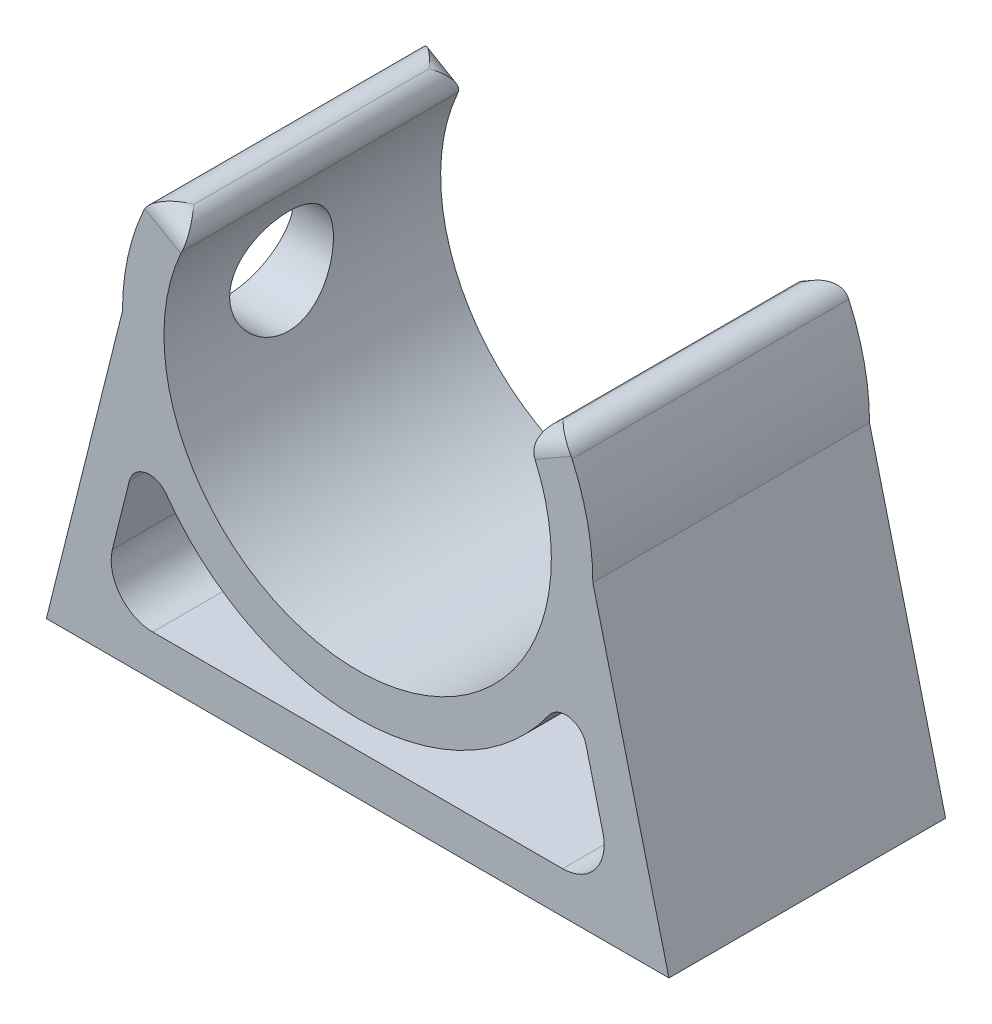
SolidWorks part; units mm, degrees
ref_plane "Front Plane" through (0, 0, 0) normal (0, 0, 1) x (1, 0, 0)
ref_plane "Top Plane" through (0, 0, 0) normal (0, 1, 0) x (1, 0, 0)
ref_plane "Right Plane" through (0, 0, 0) normal (1, 0, 0) x (0, 0, -1)
sketch "Sketch1" plane through (0, 0, 0) normal (0, 0, 1) x (1, 0, 0)
  line L0 (0.0802, 28.0625) -> (-0.0941, -32.9144) construction
  line L1 (0, 0) -> (14.7467, 8.4579) construction
  line L2 (12.1443, 6.9653) -> (14.7467, 8.4579)
  line L3 (-12.1043, 7.0346) -> (-14.6981, 8.5421)
  arc A0 (12.1443, 6.9653) -> (-12.1043, 7.0346) centre (0, 0) cw
  arc A1 (14.7467, 8.4579) -> (-14.6981, 8.5421) centre (0, 0) cw
  dimension "D1" = 14
  dimension "D2" = 3
  dimension "D3" = 120
extrude "Boss-Extrude1" add sketch "Sketch1" along normal blind 20
sketch "Sketch2" plane through (0, 0, 20) normal (0, 0, 1) x (1, 0, 0)
  line L0 (-17, 0) -> (-22.5, -22)
  line L1 (-22.5, -22) -> (22.5, -22)
  line L2 (22.5, -22) -> (17, 0)
  line L3 (17, 10.1614) -> (17, -12.2099) construction
  line L4 (0, 20.0489) -> (0, -23.3341) construction
  line L5 (-14.8153, -19) -> (14.8153, -19)
  line L6 (17.7258, -15.2724) -> (15.5978, -6.7607)
  line L7 (-17.7258, -15.2724) -> (-15.5978, -6.7607)
  arc A0 (-14.6981, 8.5421) -> (14.7467, 8.4579) centre (0, 0) ccw construction
  arc A1 (17, 0) -> (-17, 0) centre (0, 0) cw construction
  arc A2 (-14.8153, -19) -> (-17.7258, -15.2724) centre (-14.8153, -16) cw
  arc A3 (14.8153, -19) -> (17.7258, -15.2724) centre (14.8153, -16) ccw
  arc A4 (17, 0) -> (15.5978, -6.7607) centre (0, 0) cw
  arc A5 (-17, 0) -> (-15.5978, -6.7607) centre (0, 0) ccw
  point P14 (0, 0)
  point P20 (-18.6577, -19)
  point P23 (18.6577, -19)
  dimension "D1" = 22
  dimension "D5" = 3
  dimension "D2" = 45
  dimension "D3" = 3
  dimension "D4" = 3
extrude "Boss-Extrude2" add sketch "Sketch2" against normal blind 20
fillet "Fillet1" radius 1.5 2 edges at (15.5978, -6.7607, 10) (-15.5978, -6.7607, 10)
fillet "Fillet2" radius 1.5 8 edges at (-12.1043, 7.0346, 10) (-13.4012, 7.7883, 20) (-14.6981, 8.5421, 10) (-13.4012, 7.7883, 0) (14.7467, 8.4579, 10) (13.4455, 7.7116, 20) (12.1443, 6.9653, 10) (13.4455, 7.7116, 0)
sketch "Sketch3" plane through (0, 0, 0) normal (1, 0, 0) x (0, 0, -1)
  line L0 (0, 0) -> (-20, 0) construction
  circle A0 centre (-11.5, 0) radius 3.75
  point P4 (0, 0)
  dimension "D1" = 7.5
  dimension "D2" = 8.5
extrude "Cut-Extrude1" cut sketch "Sketch3" against normal blind 20
